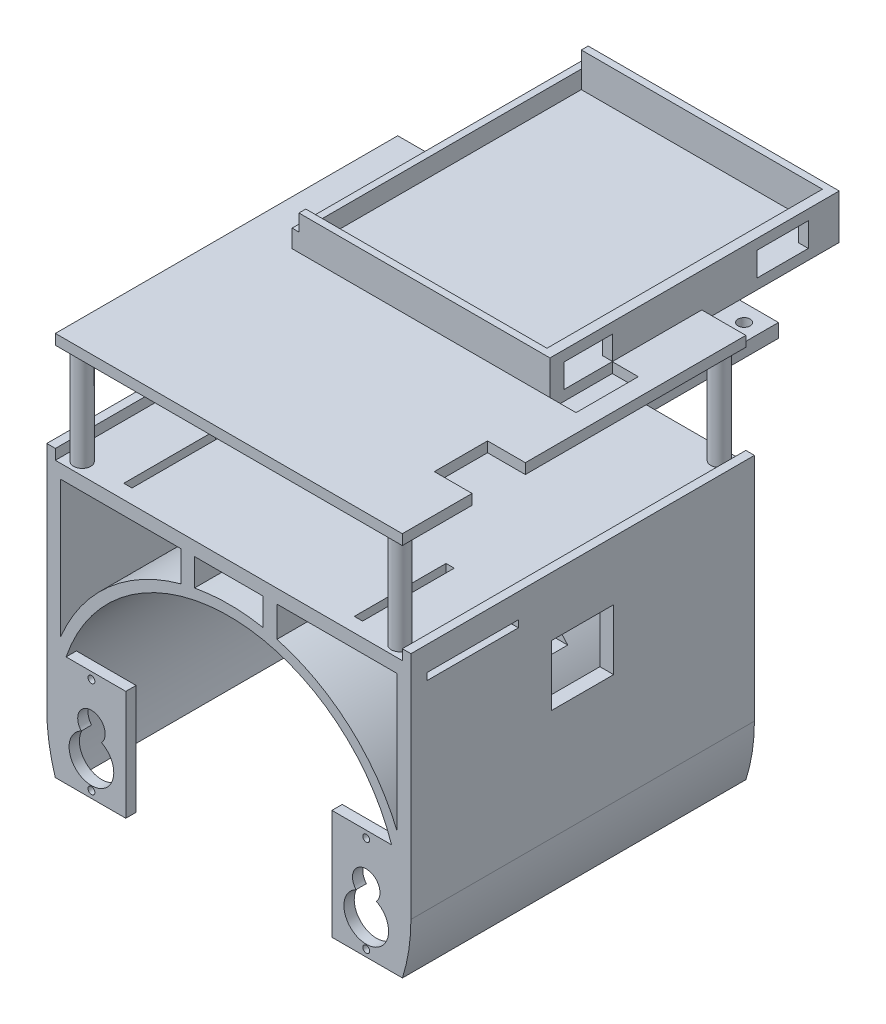
SolidWorks part; units mm, degrees
ref_plane "前视基准面" through (0, 0, 0) normal (0, 0, 1) x (1, 0, 0)
ref_plane "上视基准面" through (0, 0, 0) normal (0, 1, 0) x (1, 0, 0)
ref_plane "右视基准面" through (0, 0, 0) normal (1, 0, 0) x (0, 0, -1)
sketch "草图2" plane through (0, 0, 0) normal (0, 0, 1) x (1, 0, 0)
  line L0 (0, 0) -> (0, -50) construction
  line L1 (0, -50) -> (-133.4259, -50) construction
  line L3 (-50, -50) -> (-53, -50)
  line L4 (50, -50) -> (53, -50)
  arc A0 (50, -50) -> (-50, -50) centre (0, -50) ccw
  arc A1 (53, -50) -> (-53, -50) centre (0, -50) ccw
  circle A2 centre (0, -50) radius 53 construction
  circle A3 centre (0, -50) radius 50 construction
  dimension "D1" = 50
  dimension "D2" = 3
extrude "凸台-拉伸1" add sketch "草图2" along normal blind 100
sketch "草图3" plane through (0, 0, 100) normal (0, 0, 1) x (1, 0, 0)
  line L0 (-50, -50) -> (-30, -50) construction
  line L1 (-50, -50) -> (-47.3709, -34) construction
  line L2 (-47.3709, -34) -> (-30, -34)
  line L3 (-30, -34) -> (-30, -66)
  line L4 (0, 0) -> (0, -50) construction
  line L5 (0, -50) -> (50, -50) construction
  line L6 (-47.3709, -66) -> (-30, -66)
  line L7 (-50, -50) -> (-47.3709, -66) construction
  line L8 (-40, -34) -> (-40, -66) construction
  line L9 (50, -50) -> (53, -50) construction
  arc A0 (50, -50) -> (-50, -50) centre (0, -50) ccw construction
  circle A1 centre (-40, -36) radius 1
  circle A2 centre (-40, -64) radius 1
  arc A3 (50, -50) -> (0, 0) centre (0, -50) ccw
  arc A4 (-47.3709, -34) -> (-47.3709, -66) centre (0, -50) ccw
  circle A5 centre (-40, -56.25) radius 6.5
  arc A6 (-37.0451, -50.4605) -> (-42.9549, -50.4605) centre (-40, -47.7644) ccw
  arc M3 (-50, -50) -> (50, -50) centre (0, -50) cw
  dimension "D3" = 2
  dimension "D4" = 28
  dimension "D5" = 13
  dimension "D6" = 6.25
  dimension "D1" = 40
  dimension "D2" = 16
  dimension "D7" = 30
extrude "凸台-拉伸2" add sketch "草图3" against normal blind 3 contours A4 L6 L3 L2 A2 A1 M3 region at (-38.6854, -34.3774, 100)
sketch "草图5" plane through (0, 0, 0) normal (0, 0, -1) x (-1, 0, 0)
  line L0 (47.3709, -66) -> (50.5272, -66)
  line L1 (30, -66) -> (47.3709, -66)
  line L2 (30, -34) -> (30, -66) construction
  line L3 (47.3709, -66) -> (30, -66) construction
  line L4 (30, -66) -> (30, -34)
  line L5 (30, -34) -> (47.3709, -34)
  line L6 (47.3709, -34) -> (50.5272, -34)
  circle A0 centre (40, -56.25) radius 1.6
  arc A2 (53, -50) -> (-53, -50) centre (0, -50) ccw construction
  arc A3 (53, -50) -> (50.5272, -34) centre (0, -50) ccw
  arc A4 (50.5272, -66) -> (50.5272, -34) centre (0, -50) ccw
  arc M1 (-50, -50) -> (50, -50) centre (0, -50) cw
  line M2 (50, -50) -> (53, -50)
  dimension "D1" = 3.2
extrude "凸台-拉伸4" add sketch "草图5" against normal blind 3 contours L0 A4 L5 L4 L1 A0 M2 M1 region at (-40.4043, -50.526, 0)
sketch "草图6" plane through (0, 0, 100) normal (0, 0, 1) x (1, 0, 0)
  line L0 (-30, -66) -> (-50.5272, -66) construction
  line L1 (-53, -50) -> (-50, -50) construction
  line L2 (-47.3709, -66) -> (-50.5272, -66)
  line L3 (-53, -50) -> (-50, -50)
  line L4 (0, -50) -> (0, 0) construction
  arc A0 (-53, -50) -> (-50.5272, -66) centre (0, -50) ccw construction
  arc A1 (-50, -50) -> (-47.3709, -66) centre (0, -50) ccw construction
  arc A2 (-53, -50) -> (-50.5272, -66) centre (0, -50) ccw
  arc A3 (-50, -50) -> (-47.3709, -66) centre (0, -50) ccw
extrude "凸台-拉伸5" add sketch "草图6" against normal up to surface (97 mm away) up to face at (-41.6, -56.25, 3)
sketch "草图7" plane through (0, 0, 0) normal (0, 1, 0) x (1, 0, 0)
  line L0 (0, 0) -> (0, -100) construction
  line L1 (-53, -100) -> (53, -100) construction
  line L2 (0, -50) -> (42.6095, -50) construction
  line L3 (-7.5, -34) -> (7.5, -34)
  line L4 (-7.5, -34) -> (-7.5, -66)
  line L5 (-7.5, -66) -> (7.5, -66)
  line L6 (7.5, -34) -> (7.5, -66)
  line L7 (-7.5, -34) -> (7.5, -66) construction
  line L8 (-7.5, -66) -> (7.5, -34) construction
  point P6 (0, -50)
  dimension "D1" = 15
  dimension "D2" = 32
extrude "切除-拉伸1" cut sketch "草图7" against normal through all both and the other way through all
sketch "草图9" plane through (0, 0, 0) normal (1, 0, 0) x (0, 0, -1)
  line L0 (-50, -50) -> (-50, 15.9586) construction
  line L1 (-100, -50) -> (0, -50) construction
  line L3 (-58, -4) -> (-42, -4)
  line L4 (-58, -4) -> (-58, -16)
  line L5 (-58, -16) -> (-42, -16)
  line L6 (-42, -4) -> (-42, -16)
  line L7 (-58, -4) -> (-42, -16) construction
  line L8 (-58, -16) -> (-42, -4) construction
  point P4 (-50, -10)
  dimension "D1" = 12
  dimension "D2" = 16
  dimension "D3" = 4
extrude "切除-拉伸2" cut sketch "草图9" along normal blind 76 and the other way blind 1
sketch "草图11" plane through (0, 0, 0) normal (0, 1, 0) x (1, 0, 0)
  line L0 (53, -100) -> (53, 0)
  line L1 (0, 0) -> (0, -64.1449) construction
  line L2 (53, 0) -> (49, 0)
  line L3 (53, 0) -> (-53, 0) construction
  line L4 (49, 0) -> (49, -100)
  line L5 (-53, -100) -> (53, -100) construction
  line L6 (49, -100) -> (53, -100)
  line L7 (-10, -100) -> (-10, 0)
  line L8 (14, -100) -> (10, -100)
  line L9 (14, -100) -> (14, 0)
  line L10 (14, 0) -> (10, 0)
  line L11 (10, -100) -> (10, 0)
  line L12 (-14, 0) -> (-10, 0)
  line L13 (-14, -100) -> (-14, 0)
  line L14 (-14, -100) -> (-10, -100)
  line L15 (-49, -100) -> (-53, -100)
  line L16 (-49, 0) -> (-49, -100)
  line L17 (-53, 0) -> (-49, 0)
  line L18 (-53, -100) -> (-53, 0)
  dimension "D1" = 10
  dimension "D2" = 4
  dimension "D3" = 4
extrude "凸台-拉伸6" add sketch "草图11" along normal blind 10
sketch "草图12" plane through (0, 10, 0) normal (0, 1, 0) x (1, 0, 0)
  line L0 (-49, 0) -> (-53, 0) construction
  line L1 (53, -100) -> (-53, -100)
  line L2 (53, -100) -> (53, 0)
  line L3 (53, 0) -> (-53, 0)
  line L4 (-53, -100) -> (-53, 0)
  line L5 (-53, 0) -> (-53, -100) construction
extrude "凸台-拉伸7" add sketch "草图12" along normal blind 4
sketch "草图13" plane through (0, 0, 0) normal (0, -1, 0) x (1, 0, 0)
  line L4 (53, 100) -> (49, 100)
  line L5 (49, 100) -> (49, 0)
  line L7 (53, 0) -> (53, 100)
  line L9 (49, 100) -> (49, 0)
  line L11 (53, 0) -> (53, 100)
  line L12 (-49, 0) -> (-49, 100)
  line L13 (-49, 100) -> (-53, 100)
  line L14 (-53, 100) -> (-53, 0)
  line L16 (-49, 0) -> (-49, 100)
  line L18 (-53, 100) -> (-53, 0)
  line L20 (53, 100) -> (49, 100)
  line L22 (-49, 100) -> (-53, 100)
  line L24 (49, 0) -> (53, 0)
  line L25 (49, 0) -> (53, 0)
  line L26 (-53, 0) -> (-49, 0)
  line L27 (-53, 0) -> (-49, 0)
  dimension "D1" = 0
  dimension "D2" = 0
extrude "凸台-拉伸8" add sketch "草图13" along normal up to surface (50 mm away) up to face at (0, 2.7333, 50)
sketch "草图14" plane through (0, 14, 0) normal (0, 1, 0) x (1, 0, 0)
  line L0 (0, 0) -> (0, -118.4554) construction
  line L6 (53, 0) -> (-53, 0) construction
  line L7 (53, -100) -> (50.5, -100)
  line L9 (53, -100) -> (53, 0)
  line L10 (53, 0) -> (50.5, 0)
  line L11 (50.5, -100) -> (50.5, 0)
  line L12 (-50.5, -100) -> (-50.5, 0)
  line L13 (-53, 0) -> (-50.5, 0)
  line L14 (-53, -100) -> (-53, 0)
  line L15 (-53, -100) -> (-50.5, -100)
  dimension "D1" = 101
extrude "凸台-拉伸9" add sketch "草图14" along normal blind 3
mirror "镜向1" about plane through (0, 0, 0) normal (1, 0, 0) of "凸台-拉伸4", "凸台-拉伸2"
sketch "草图15" plane through (0, 0, 3) normal (0, 0, 1) x (1, 0, 0)
  line L0 (50, -50) -> (53, -50) construction
  line L1 (30, -66) -> (50.5272, -66) construction
  line L2 (50, -50) -> (53, -50)
  line L3 (47.3709, -66) -> (50.5272, -66)
  arc A0 (50.5272, -66) -> (53, -50) centre (0, -50) ccw construction
  arc A1 (47.3709, -66) -> (50, -50) centre (0, -50) ccw construction
  arc A2 (50.5272, -66) -> (53, -50) centre (0, -50) ccw
  arc A3 (47.3709, -66) -> (50, -50) centre (0, -50) ccw
extrude "凸台-拉伸10" add sketch "草图15" along normal up to surface (97 mm away) up to face at (2.7578, -24.7178, 100)
ref_plane "基准面1" through (19.5959, 0, 0) normal (1, 0, 0) x (0, 0, -1)
sketch "草图16" plane through (19.5959, 0, 0) normal (1, 0, 0) x (0, 0, -1)
  line L0 (-58, -4) -> (-42, -4) construction
  line L1 (-56.0363, -4) -> (-43.9637, -4)
  line L2 (-50, -4) -> (-50, -39.7946) construction
  line L3 (-50, -9.25) -> (-37.4011, -9.25) construction
  line L4 (-56.0363, -14.5) -> (-43.9637, -14.5)
  line L5 (-58, -4) -> (-42, -4) construction
  line L6 (-57.6444, 0) -> (-42.3556, 0)
  line L7 (-57.6444, -18.5) -> (-42.3556, -18.5)
  arc A0 (-43.9637, -14.5) -> (-43.9637, -4) centre (-50, -9.25) ccw
  arc A1 (-56.0363, -4) -> (-56.0363, -14.5) centre (-50, -9.25) ccw
  arc A2 (-42.3556, -18.5) -> (-42.3556, 0) centre (-50, -9.25) ccw
  arc A3 (-57.6444, 0) -> (-57.6444, -18.5) centre (-50, -9.25) ccw
  dimension "D1" = 10.5
  dimension "D2" = 8
  dimension "D3" = 4
extrude "凸台-拉伸11" add sketch "草图16" along normal blind 10
sketch "草图17" plane through (29.5959, 0, 0) normal (1, 0, 0) x (0, 0, -1)
  line L4 (-58, -9.7001) -> (-61.9916, -9.7001)
  line L6 (-58, -9.7001) -> (-61.9916, -9.7001)
  line L21 (-57.6444, -18.5) -> (-42.3556, -18.5)
  line L23 (-42, -9.7001) -> (-42, -9.25)
  line L24 (-42, -9.7001) -> (-42, -9.25)
  line L29 (-57.6444, -18.5) -> (-42.3556, -18.5)
  line L32 (-38.0084, -9.7001) -> (-42, -9.7001)
  line L34 (-38.0084, -9.7001) -> (-42, -9.7001)
  line L35 (-43.9637, -14.5) -> (-56.0363, -14.5)
  line L36 (-43.9637, -14.5) -> (-56.0363, -14.5)
  line L37 (-58, -9.25) -> (-58, -9.7001)
  line L38 (-58, -9.25) -> (-58, -9.7001)
  arc A4 (-61.9916, -9.7001) -> (-57.6444, -18.5) centre (-50, -9.25) ccw
  arc A5 (-42.3556, -18.5) -> (-38.0084, -9.7001) centre (-50, -9.25) ccw
  arc A6 (-43.9637, -14.5) -> (-42, -9.25) centre (-50, -9.25) ccw
  arc A8 (-61.9916, -9.7001) -> (-57.6444, -18.5) centre (-50, -9.25) ccw
  arc A9 (-42.3556, -18.5) -> (-38.0084, -9.7001) centre (-50, -9.25) ccw
  arc A18 (-43.9637, -14.5) -> (-42, -9.25) centre (-50, -9.25) ccw
  arc A20 (-58, -9.25) -> (-56.0363, -14.5) centre (-50, -9.25) ccw
  arc A21 (-58, -9.25) -> (-56.0363, -14.5) centre (-50, -9.25) ccw
  dimension "D1" = 0
extrude "凸台-拉伸12" add sketch "草图17" along normal up to surface up to face at (27.0387, -8.6465, 50.1201)
sketch "草图18" plane through (0, 0, 0) normal (0, 0, -1) x (-1, 0, 0)
  line L0 (0, 0) -> (0, 31.7451) construction
  line L1 (-50.5, 14) -> (50.5, 14) construction
  line L2 (20, 10) -> (-20, 10)
  line L3 (20, 10) -> (20, 14)
  line L4 (20, 14) -> (-20, 14)
  line L5 (-20, 10) -> (-20, 14)
  line L6 (20, 10) -> (-20, 14) construction
  line L7 (20, 14) -> (-20, 10) construction
  line L8 (-10, 10) -> (10, 10) construction
  point P3 (0, 12)
  dimension "D1" = 40
extrude "凸台-拉伸13" add sketch "草图18" along normal blind 40
sketch "草图19" plane through (0, 10, 0) normal (0, -1, 0) x (1, 0, 0)
  line L0 (0, 0) -> (0, -40) construction
  line L1 (20, -40) -> (-20, -40) construction
  line L2 (0, -20) -> (-35.3384, -20) construction
  line L3 (20, -40) -> (20, 0) construction
  circle A0 centre (15, -35) radius 1.75
  circle A1 centre (-15, -35) radius 1.75
  circle A2 centre (-15, -5) radius 1.75
  circle A3 centre (15, -5) radius 1.75
  circle A4 centre (0, -20) radius 12.5
  dimension "D1" = 3.5
  dimension "D2" = 5
  dimension "D3" = 5
  dimension "D4" = 25
extrude "切除-拉伸3" cut sketch "草图19" against normal blind 50
sketch "草图21" plane through (53, 0, 0) normal (1, 0, 0) x (0, 0, -1)
  line L1 (-59.1426, -0.1553) -> (-40.9842, -0.1553)
  line L2 (-59.1426, -0.1553) -> (-59.1426, -17.7908)
  line L3 (-59.1426, -17.7908) -> (-40.9842, -17.7908)
  line L4 (-40.9842, -0.1553) -> (-40.9842, -17.7908)
extrude "切除-拉伸4" cut sketch "草图21" against normal blind 6
sketch "草图22" plane through (53, 0, 0) normal (1, 0, 0) x (0, 0, -1)
  line L1 (-95.3558, 9.9014) -> (-68.7105, 9.9014)
  line L2 (-95.3558, 9.9014) -> (-95.3558, 7.8718)
  line L3 (-95.3558, 7.8718) -> (-68.7105, 7.8718)
  line L4 (-68.7105, 9.9014) -> (-68.7105, 7.8718)
extrude "切除-拉伸5" cut sketch "草图22" against normal blind 113
sketch "草图23" plane through (0, 14, 0) normal (0, 1, 0) x (1, 0, 0)
  line L6 (32.3595, -69.1302) -> (34.7547, -69.1302)
  line L7 (32.3595, -69.1302) -> (32.3595, -95.8374)
  line L8 (32.3595, -95.8374) -> (34.7547, -95.8374)
  line L9 (34.7547, -69.1302) -> (34.7547, -95.8374)
  line L10 (-32.3595, -69.1302) -> (-34.7513, -69.1302)
  line L11 (-32.3595, -69.1302) -> (-32.3595, -95.8374)
  line L12 (-32.3595, -95.8374) -> (-34.7513, -95.8374)
  line L13 (-34.7513, -69.1302) -> (-34.7513, -95.8374)
  point P6 (0, 0)
extrude "切除-拉伸6" cut sketch "草图23" against normal blind 10
sketch "草图24" plane through (0, 14, 0) normal (0, 1, 0) x (1, 0, 0)
  line L1 (-50.5, -100) -> (-50.5, 0) construction
  line L3 (50.5, 0) -> (50.5, -100) construction
  circle A0 centre (0, 36.9082) radius 2.5
  circle A1 centre (46.1817, -3.3888) radius 2.5
  circle A2 centre (-46.3183, -3.3888) radius 2.5
  circle A3 centre (-46.3183, -96.3806) radius 2.5
  circle A4 centre (46.1817, -96.3806) radius 2.5
  dimension "D1" = 4.1817
  dimension "D2" = 92.5
  dimension "D3" = 4.3183
extrude "凸台-拉伸14" add sketch "草图24" along normal blind 29
sketch "草图25" plane through (0, 43, 0) normal (0, 1, 0) x (1, 0, 0)
  line L1 (-50.5, 40.0042) -> (50.5, 40.0042)
  line L2 (-50.5, 40.0042) -> (-50.5, -100)
  line L3 (-50.5, -100) -> (50.5, -100)
  line L4 (50.5, 40.0042) -> (50.5, -100)
  dimension "D1" = 101
extrude "凸台-拉伸15" add sketch "草图25" along normal blind 3
sketch "草图26" plane through (0, 46, 0) normal (0, 1, 0) x (1, 0, 0)
  line L2 (50.5, 40.0042) -> (-50.5, 40.0042) construction
  line L3 (34.7999, -42.1958) -> (34.7999, 38.0042)
  line L4 (-35.4001, 40.0042) -> (35.7625, 40.0042)
  line L5 (-35.4001, 40.0042) -> (-35.4001, 38.0042)
  line L6 (-35.4001, 38.0042) -> (34.7999, 38.0042)
  line L8 (-35.4001, -42.1958) -> (34.7999, -42.1958)
  line L9 (-35.4001, -42.1958) -> (-35.4001, -44.1958)
  line L10 (-35.4001, -44.1958) -> (35.6791, -44.1958)
  line L16 (35.6791, -44.1958) -> (37.6791, -44.1958)
  line L17 (37.6791, -44.1958) -> (37.6791, 40.0042)
  line L18 (37.6791, 40.0042) -> (35.7625, 40.0042)
  point P4 (0, 0)
  point P10 (0, 0)
extrude "凸台-拉伸16" add sketch "草图26" along normal blind 10
sketch "草图28" plane through (37.6791, 0, 0) normal (1, 0, 0) x (0, 0, -1)
  line L0 (-44.1958, 46) -> (40.0042, 46) construction
  line L1 (-40.1194, 52.9216) -> (-25.9749, 52.9216)
  line L2 (-40.1194, 52.9216) -> (-40.1194, 46)
  line L3 (-40.1194, 46) -> (-25.9749, 46)
  line L4 (-25.9749, 52.9216) -> (-25.9749, 46)
  line L5 (40.0042, 56) -> (40.0042, 46) construction
  line L6 (16.0042, 53) -> (31.0042, 53)
  line L7 (16.0042, 53) -> (16.0042, 46)
  line L8 (16.0042, 46) -> (31.0042, 46)
  line L9 (31.0042, 53) -> (31.0042, 46)
  dimension "D1" = 24
  dimension "D2" = 15
  dimension "D3" = 7
extrude "切除-拉伸7" cut sketch "草图28" against normal blind 3
sketch "草图29" plane through (0, 46, 0) normal (0, 1, 0) x (1, 0, 0)
  line L0 (37.6791, -44.1958) -> (37.6791, 40.0042) construction
  line L1 (37.6791, -26.0652) -> (45.2647, -26.0652)
  line L2 (37.6791, -26.0652) -> (37.6791, -44.1958)
  line L3 (37.6791, -44.1958) -> (45.2647, -44.1958)
  line L4 (45.2647, -26.0652) -> (45.2647, -44.1958)
extrude "切除-拉伸8" cut sketch "草图29" against normal blind 3
sketch "草图30" plane through (0, 46, 0) normal (0, 1, 0) x (1, 0, 0)
  line L0 (50.5, -100) -> (50.5, 40.0042) construction
  line L1 (50.5, -64.1915) -> (39.5, -64.1915)
  line L2 (50.5, -64.1915) -> (50.5, -79.6958)
  line L3 (50.5, -79.6958) -> (39.5, -79.6958)
  line L4 (39.5, -64.1915) -> (39.5, -79.6958)
  line L5 (37.6791, -44.1958) -> (45.2647, -44.1958) construction
  dimension "D1" = 35.5
  dimension "D2" = 15.5043
extrude "切除-拉伸9" cut sketch "草图30" against normal blind 3
sketch "草图31" plane through (0, 46, 0) normal (0, 1, 0) x (1, 0, 0)
  line L1 (37.6791, 40.0042) -> (50.5, 40.0042)
  line L2 (37.6791, 40.0042) -> (37.6791, 0)
  line L3 (37.6791, 0) -> (50.5, 0)
  line L4 (50.5, 40.0042) -> (50.5, 0)
  line L5 (-50.5, 40.0042) -> (-37.3959, 40.0042)
  line L6 (-50.5, 40.0042) -> (-50.5, -0.3369)
  line L7 (-50.5, -0.3369) -> (-37.3959, -0.3369)
  line L8 (-37.3959, 40.0042) -> (-37.3959, -0.3369)
extrude "切除-拉伸10" cut sketch "草图31" against normal blind 3
sketch "草图32" plane through (0, 46, 0) normal (0, 1, 0) x (1, 0, 0)
  line L0 (-35.4001, 38.0042) -> (-35.4001, -42.1958)
  line L1 (34.7999, -42.1958) -> (-35.4001, -42.1958) construction
  line L2 (-37.3804, -42.1958) -> (-37.3804, -44.1958)
  line L4 (-35.4001, 40.0042) -> (-37.3959, 40.0042) construction
  line L5 (-36.398, 40.0042) -> (-35.4001, 40.0042)
  line L6 (-37.3804, -44.1958) -> (-35.4001, -44.1958)
  line L7 (-35.4001, -44.1958) -> (-35.4001, -42.1958)
  line L8 (-35.4001, 38.0042) -> (-35.4001, 40.0042)
  line L9 (-36.398, 40.0042) -> (-37.3959, 40.0042)
  line L10 (-37.3959, 40.0042) -> (-37.3804, -42.1958)
extrude "凸台-拉伸17" add sketch "草图32" along normal blind 5.2
